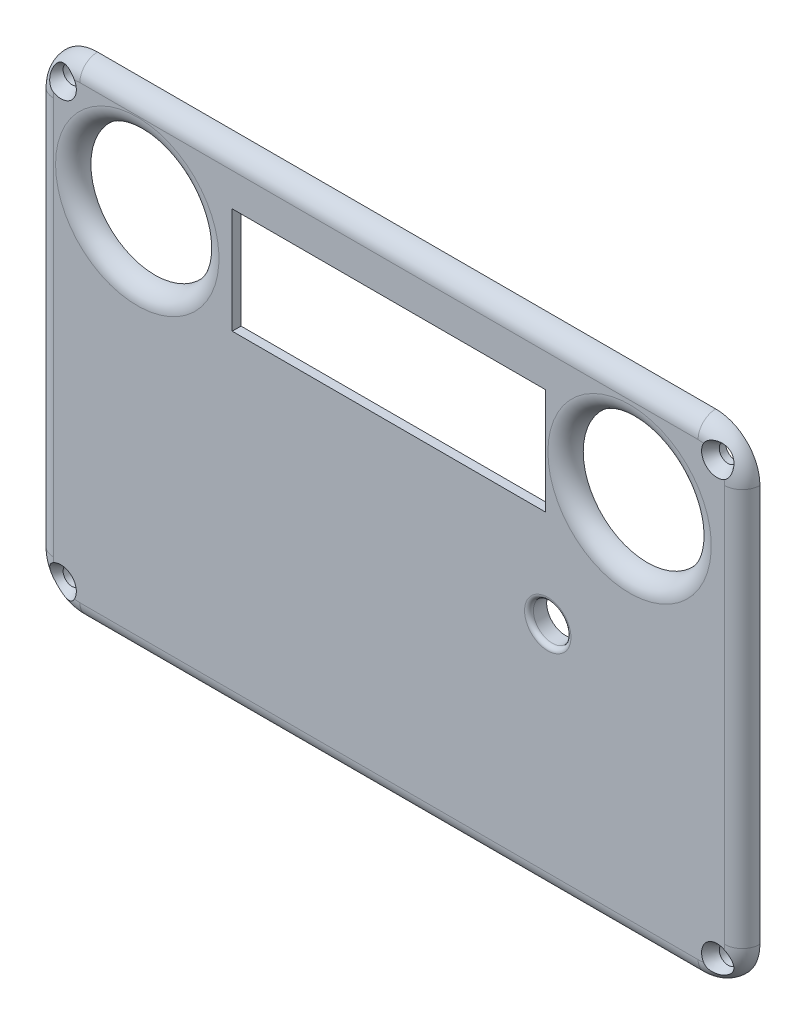
SolidWorks part; units mm, degrees
ref_plane "Ön Düzlem" through (0, 0, 0) normal (0, 0, 1) x (1, 0, 0)
ref_plane "Üst Düzlem" through (0, 0, 0) normal (0, 1, 0) x (1, 0, 0)
ref_plane "Sağ Düzlem" through (0, 0, 0) normal (1, 0, 0) x (0, 0, -1)
sketch "Çizim1" plane through (0, 0, 0) normal (0, 0, 1) x (1, 0, 0)
  line L0 (0, 55) -> (0, -55) construction
  line L1 (-80, -55) -> (80, -55)
  line L2 (-80, -55) -> (-80, 55)
  line L3 (-80, 55) -> (80, 55)
  line L4 (80, -55) -> (80, 55)
  line L5 (-80, -55) -> (80, 55) construction
  line L6 (-80, 55) -> (80, -55) construction
  line L8 (-35.5, 43.5) -> (35.5, 43.5)
  line L9 (-35.5, 43.5) -> (-35.5, 19.5)
  line L10 (-35.5, 19.5) -> (35.5, 19.5)
  line L11 (35.5, 43.5) -> (35.5, 19.5)
  circle A0 centre (-57, 32.25) radius 14.5
  circle A4 centre (54.4916, 31.612) radius 14.5
  circle A5 centre (35.9584, -2.2) radius 4.25
  circle A6 centre (-74.292, -49.1927) radius 2
  circle A7 centre (-74.2916, 49.1931) radius 2.0005
  circle A8 centre (74.292, 49.1927) radius 2
  circle A9 centre (74.292, -49.1927) radius 2
  point P0 (0, 0)
  point P16 (0, 43.5)
  dimension "D3" = 29
  dimension "D4" = 29
  dimension "D7" = 8.5
  dimension "D9" = 4.001
  dimension "D10" = 4
  dimension "D11" = 4
  dimension "D12" = 4
  dimension "D1" = 160
  dimension "D2" = 110
  dimension "D5" = 24
  dimension "D6" = 71
  dimension "D8" = 11.5
  dimension "D13" = 12.75
  dimension "D14" = 21.5
extrude "Yükseklik-Ekstrüzyon1" add sketch "Çizim1" along normal blind 4
fillet "Radyus1" radius 10 4 edges at (-80, -55, 2) (80, -55, 2) (80, 55, 2) (-80, 55, 2)
fillet "Radyus2" radius 4 2 edges at (-42.5, 32.25, 4) (68.9916, 31.612, 4)
sketch "Çizim2" plane through (0, 0, 0) normal (0, 0, -1) x (-1, 0, 0)
  line L0 (-35.5, 43.5) -> (35.5, 43.5) construction
  line L1 (-38.15, 49.3) -> (38.15, 49.3)
  line L2 (-38.15, 49.3) -> (-38.15, 16.5)
  line L3 (-38.15, 16.5) -> (38.15, 16.5)
  line L4 (38.15, 49.3) -> (38.15, 16.5)
  line L5 (35.5, 19.5) -> (-35.5, 19.5) construction
  point P8 (0, 19.5)
  point P9 (0, 16.5)
  dimension "D1" = 32.8
  dimension "D2" = 76.3
  dimension "D3" = 5.8
extrude "Kes-Ekstrüzyon1" cut sketch "Çizim2" against normal blind 2
fillet "Radyus3" radius 4 8 edges at (-77.0711, 52.0711, 4) (0, 55, 4) (77.0711, 52.0711, 4) (80, 0, 4) (77.0711, -52.0711, 4) (0, -55, 4) (-77.0711, -52.0711, 4) (-80, 0, 4)
ref_plane "Düzlem1" through (0, 0, 1.5) normal (0, 0, 1) x (1, 0, 0)
sketch "Çizim4" plane through (0, 0, 4) normal (0, 0, 1) x (1, 0, 0)
  circle A0 centre (-74.292, -49.1927) radius 3.5
  dimension "D1" = 7
sketch "Çizim5" plane through (0, 0, 1.5) normal (0, 0, 1) x (1, 0, 0)
  circle A0 centre (-74.292, -49.1927) radius 2
  dimension "D1" = 4
loft "Kes-Loft1" cut profiles "Çizim5", "Çizim4" connector at (-74.6828, -51.1542, 1.5) connector at (-75.7343, -52.3817, 4)
mirror "Aynalama1" about plane through (0, 0, 0) normal (0, 1, 0) of "Kes-Loft1" second plane through (0, 0, 0) second plane normal (1, 0, 0)
fillet "Radyus4" radius 1 1 edges at (40.2084, -2.2, 4)
